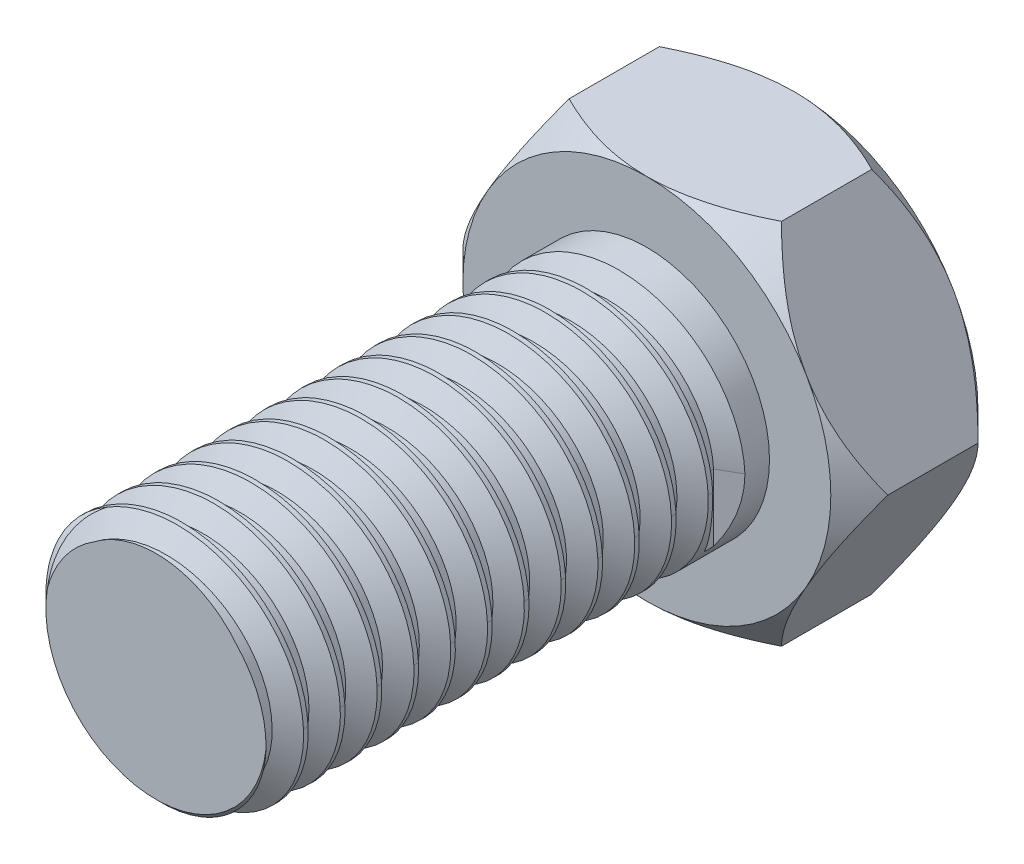
SolidWorks part; units mm, degrees
ref_plane "Front Plane" through (0, 0, 0) normal (0, 0, 1) x (1, 0, 0)
ref_plane "Top Plane" through (0, 0, 0) normal (0, 1, 0) x (1, 0, 0)
ref_plane "Right Plane" through (0, 0, 0) normal (1, 0, 0) x (0, 0, -1)
sketch "Sketch1" plane through (0, 0, 0) normal (0, 0, 1) x (1, 0, 0)
  line L1 (8.6603, 0) -> (4.3301, 7.5)
  line L2 (4.3301, 7.5) -> (-4.3301, 7.5)
  line L3 (-4.3301, 7.5) -> (-8.6603, 0)
  line L4 (-8.6603, 0) -> (-4.3301, -7.5)
  line L5 (-4.3301, -7.5) -> (4.3301, -7.5)
  line L6 (4.3301, -7.5) -> (8.6603, 0)
  circle A0 centre (0, 0) radius 7.5 construction
  dimension "D1" = 15
extrude "Boss-Extrude1" add sketch "Sketch1" along normal mid plane 6
sketch "Sketch2" plane through (0, 0, 3) normal (0, 0, 1) x (1, 0, 0)
  circle A0 centre (0, 0) radius 7.5
extrude "Cut-Extrude1" cut sketch "Sketch2" against normal through all draft 45 flip side to cut
mirror "Mirror1" about plane through (0, 0, 0) normal (0, 0, 1) of "Cut-Extrude1"
sketch "Sketch3" plane through (0, 0, 3) normal (0, 0, 1) x (1, 0, 0)
  circle A0 centre (0, 0) radius 5
extrude "Boss-Extrude2" add sketch "Sketch3" along normal blind 20
chamfer "Chamfer1" distance 0.5 angle 45 1 edges at (5, 0, 23)
thread "Thread1" pitch 1.5 method cut profile "Thread Profile1" start angle 0, offset 1, length 0, pitch 1.5, diameter 10
ref_plane "Plane1" through (5, 0, 4) normal (0, -1, 0) x (1, 0, 0)
sketch "Thread Profile1" plane through (5, 0, 4) normal (0, -1, 0) x (1, 0, 0)
  line L0 (0, 0) -> (0, 1.5) construction
  line L11 (0, 0) -> (0, 1.3125)
  line L12 (0, 1.3125) -> (-0.8119, 0.8437)
  line L13 (-0.8119, 0.8437) -> (-0.8119, 0.4687)
  line L15 (-0.8119, 0.4687) -> (0, 0)
  line L17 (-0.8119, 0.6562) -> (0, 0.6562) construction
  point P2 (0, 0)
  dimension "Pitch" = 1.5
  dimension "Profile_Angle" = 60
  dimension "Profile_Land" = 0.375
  dimension "Profile_Height" = 0.8119
sketch "Sketch7" plane through (0, 0, 0) normal (0, 1, 0) x (1, 0, 0)
  line L4 (5, -4) -> (4.1881, -4.4687)
  line L5 (4.1881, -4.4687) -> (4.1881, -4.8437)
  line L6 (4.1881, -4.8437) -> (5, -5.3125)
  line L7 (5, -5.3125) -> (5, -4)
  line L8 (5, -4) -> (4.1881, -4.4687)
  line L9 (4.1881, -4.4687) -> (4.1881, -4.8437)
  line L10 (4.1881, -4.8437) -> (5, -5.3125)
  line L11 (5, -5.3125) -> (5, -4)
  dimension "D1" = 0
extrude "Cut-Extrude2" cut sketch "Sketch7" against normal through all
